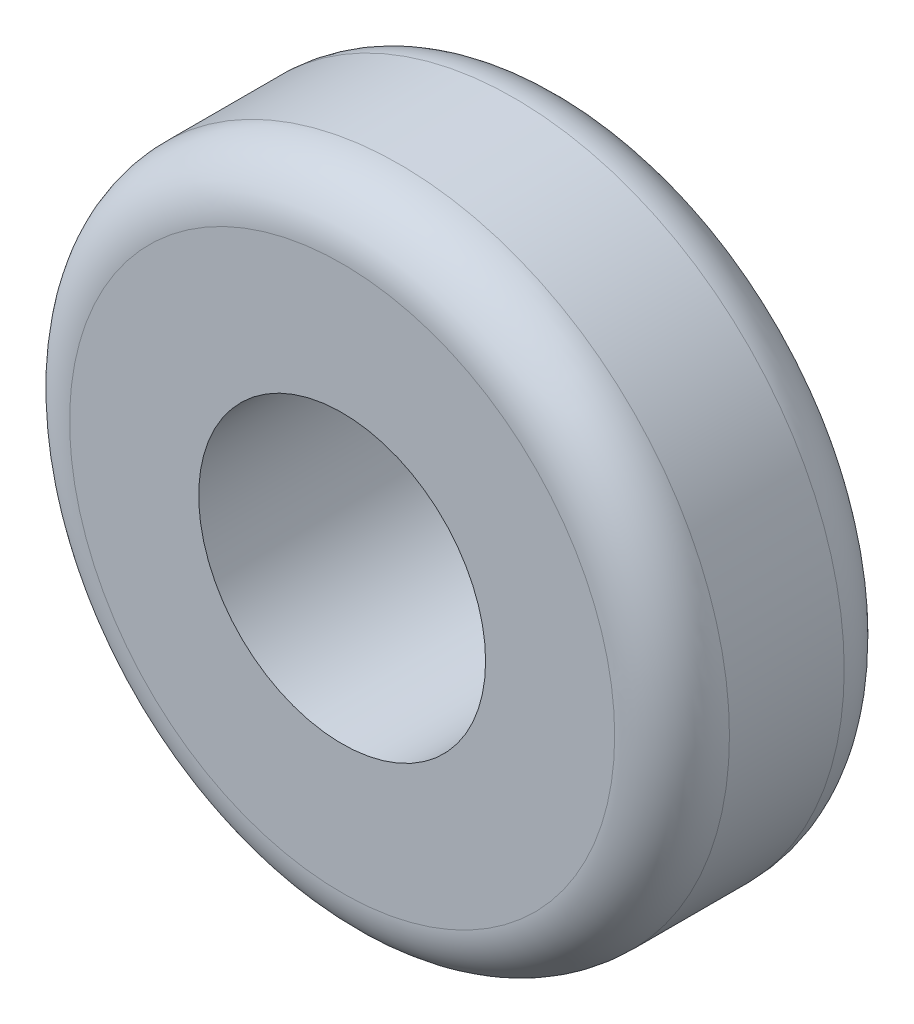
SolidWorks part; units mm, degrees
ref_plane "Front Plane" through (0, 0, 0) normal (0, 0, 1) x (1, 0, 0)
ref_plane "Top Plane" through (0, 0, 0) normal (0, 1, 0) x (1, 0, 0)
ref_plane "Right Plane" through (0, 0, 0) normal (1, 0, 0) x (0, 0, -1)
sketch "Sketch2" plane through (0, 0, 0) normal (0, 0, 1) x (1, 0, 0)
  circle A0 centre (0, 0) radius 8.625
  circle A1 centre (0, 0) radius 3.75
  dimension "D1" = 17.25
  dimension "D2" = 7.5
extrude "Boss-Extrude1" add sketch "Sketch2" along normal mid plane 6
fillet "Fillet1" radius 1.5 2 edges at (8.625, 0, -3) (8.625, 0, 3)
